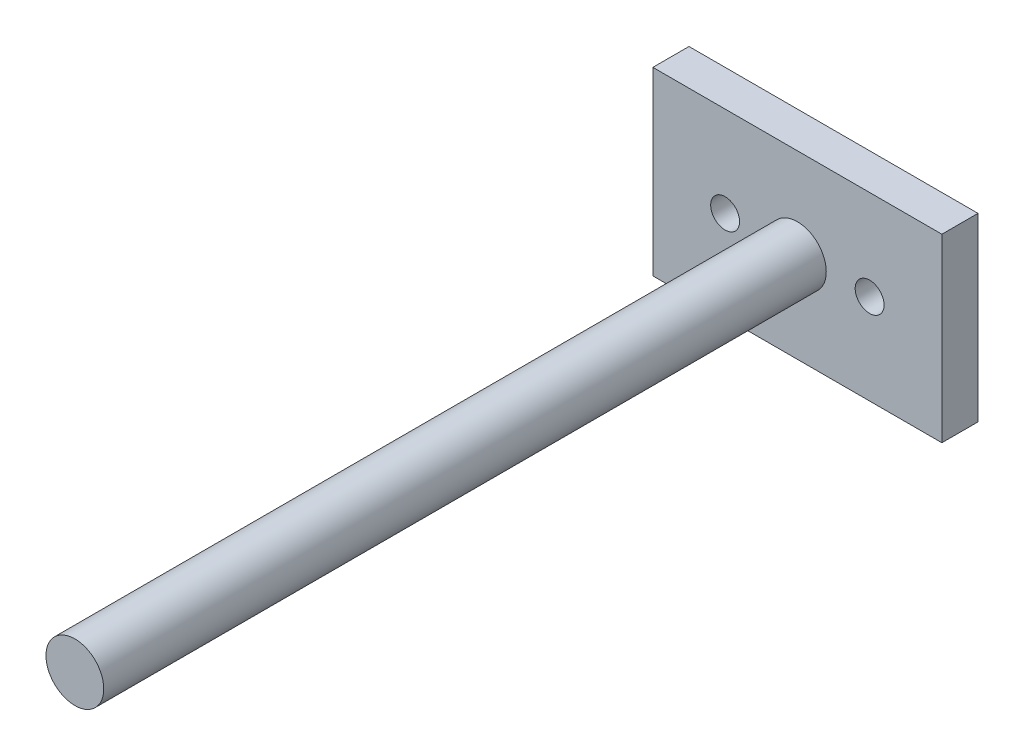
SolidWorks part; units mm, degrees
ref_plane "Plano frontal" through (0, 0, 0) normal (0, 0, 1) x (1, 0, 0)
ref_plane "Plano superior" through (0, 0, 0) normal (0, 1, 0) x (1, 0, 0)
ref_plane "Plano direito" through (0, 0, 0) normal (1, 0, 0) x (0, 0, -1)
sketch "Esboço1" plane through (0, 0, 0) normal (0, 0, 1) x (1, 0, 0)
  line L1 (-20, -12.5) -> (20, -12.5)
  line L2 (-20, -12.5) -> (-20, 12.5)
  line L3 (-20, 12.5) -> (20, 12.5)
  line L4 (20, -12.5) -> (20, 12.5)
  line L5 (0, 12.5) -> (0, -12.5) construction
  line L6 (-20, 0) -> (20, 0) construction
  circle A0 centre (0, 0) radius 4
  circle A1 centre (10, 0) radius 2
  circle A2 centre (-10, 0) radius 2
extrude "Ressalto-extrusão1" add sketch "Esboço1" along normal blind 100 contours A0 region at (0, 0, 0)
extrude "Ressalto-extrusão2" add sketch "Esboço1<3>" against normal blind 5 separate body contours A0 | L1 L4 L3 L2 A0 region at (-19.5283, 0, 0) region at (0, 0, 0)
sketch "Esboço1<3>" plane through (0, 0, 0) normal (0, 0, 1) x (1, 0, 0) same geometry as "Esboço1"
